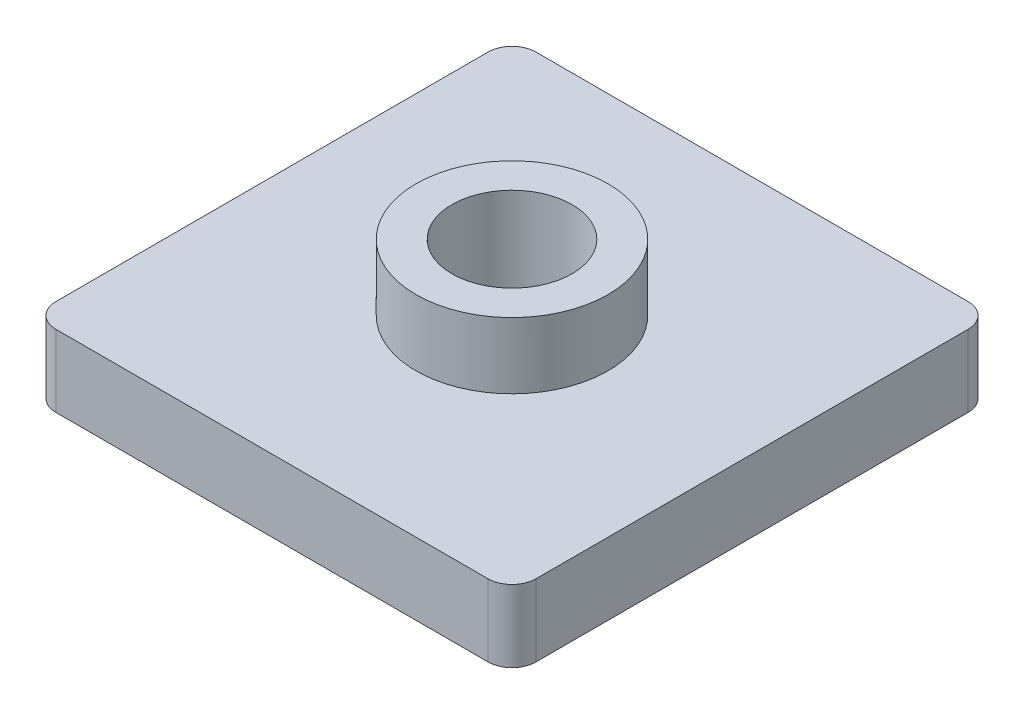
SolidWorks part; units mm, degrees
ref_plane "Front Plane" through (0, 0, 0) normal (0, 0, 1) x (1, 0, 0)
ref_plane "Top Plane" through (0, 0, 0) normal (0, 1, 0) x (1, 0, 0)
ref_plane "Right Plane" through (0, 0, 0) normal (1, 0, 0) x (0, 0, -1)
sketch "Sketch1" plane through (0, 0, 0) normal (0, 1, 0) x (1, 0, 0)
  line L1 (-10, 10) -> (10, 10)
  line L2 (-10, 10) -> (-10, -10)
  line L3 (-10, -10) -> (10, -10)
  line L4 (10, 10) -> (10, -10)
  line L5 (-10, 10) -> (10, -10) construction
  line L6 (-10, -10) -> (10, 10) construction
  circle A0 centre (0, 0) radius 4
  point P0 (0, 0)
  dimension "D3" = 8
  dimension "D1" = 20
  dimension "D2" = 20
extrude "Boss-Extrude1" add sketch "Sketch1" along normal blind 3 contours L2 L3 L4 L1
fillet "Fillet1" radius 1 4 edges at (-10, 1.5, -10) (10, 1.5, -10) (10, 1.5, 10) (-10, 1.5, 10)
extrude "Boss-Extrude2" add sketch "Sketch1<3>" along normal blind 5.75 contours A0
sketch "Sketch1<3>" plane through (0, 0, 0) normal (0, 1, 0) x (1, 0, 0) same geometry as "Sketch1"
sketch "Sketch2" plane through (0, 5.75, 0) normal (0, 1, 0) x (1, 0, 0)
  circle A0 centre (0, 0) radius 2.5
  dimension "D1" = 5
extrude "Cut-Extrude1" cut sketch "Sketch2" against normal up to surface (5.75 mm away) up to face at (0, 0, 0)
